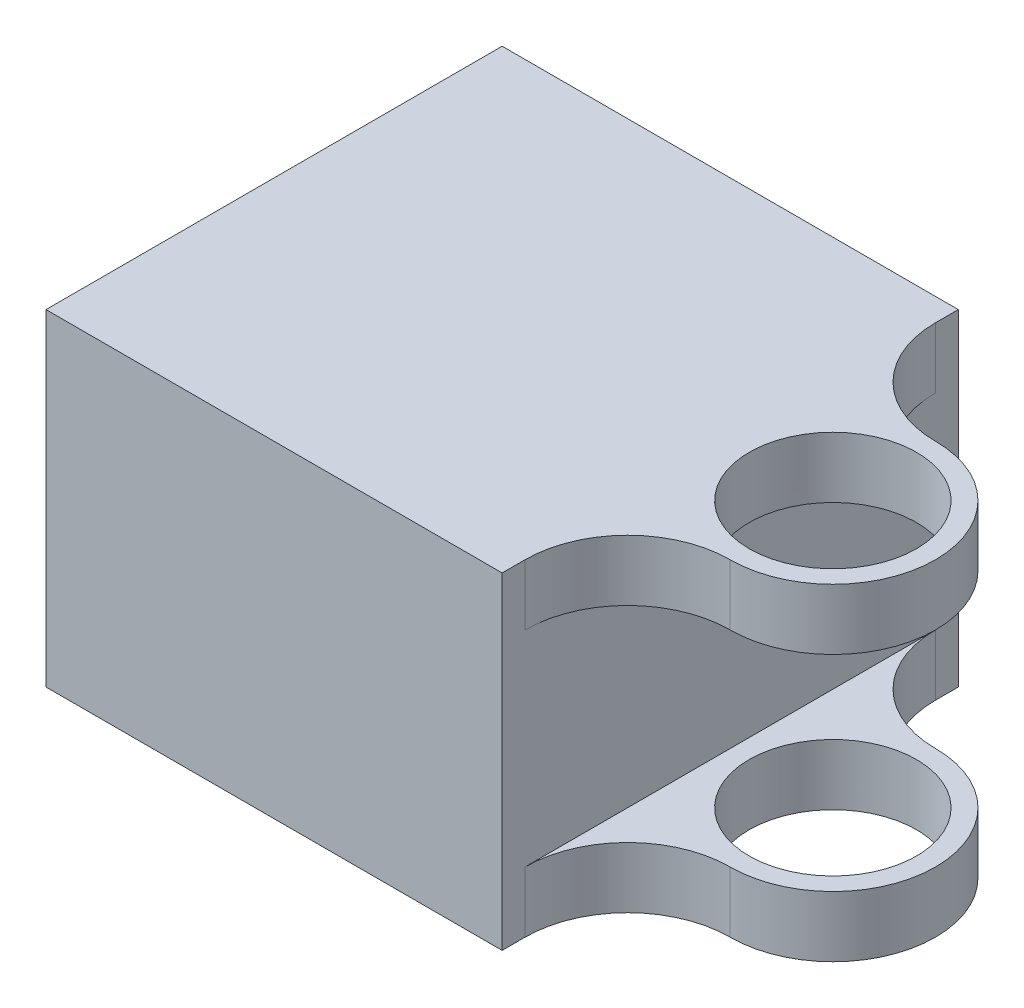
SolidWorks part; units mm, degrees
ref_plane "Спереди" through (0, 0, 0) normal (0, 0, 1) x (1, 0, 0)
ref_plane "Сверху" through (0, 0, 0) normal (0, 1, 0) x (1, 0, 0)
ref_plane "Справа" through (0, 0, 0) normal (1, 0, 0) x (0, 0, -1)
sketch "Эскиз1" plane through (0, 0, 0) normal (0, 1, 0) x (1, 0, 0)
  line L0 (11, 0) -> (13.5, 0)
  line L1 (-13.5, -30) -> (-13.5, 30)
  line L2 (-13.5, 30) -> (-73.5, 30)
  line L3 (-73.5, 30) -> (-73.5, -30)
  line L4 (-73.5, -30) -> (-13.5, -30)
  line L5 (0, -13.5) -> (-13.5, -13.5) construction
  circle A0 centre (0, 0) radius 11
  circle A1 centre (0, 0) radius 13.5
  arc A3 (0, -13.5) -> (-13.5, -27) centre (0, -27) ccw
  arc A5 (-13.5, 27) -> (0, 13.5) centre (0, 27) ccw
  point P9 (-13.5, 0)
extrude "Бобышка-Вытянуть1" add sketch "Эскиз1" along normal mid plane 43 contours A1 A0 | A3 L5 L1 | L5 A1 L1 | A5 L1 A1 | L3 L4 L1 L2 region at (9.2759, 0, 9.2759) region at (-10.4845, 0, -13.5) region at (-10.4845, 0, 16.5155) region at (-10.4845, 0, 10.4845) region at (-43.5, 0, 0)
sketch "Эскиз2" plane through (0, 0, 0) normal (0, 0, 1) x (1, 0, 0)
  line L1 (0, 21.5) -> (0, -21.5) construction
  line L2 (0, 13.5) -> (13.5, 13.5)
  line L3 (13.5, -21.5) -> (13.5, 21.5) construction
  line L4 (13.5, 13.5) -> (13.5, -13.5)
  line L5 (13.5, -13.5) -> (-13.5, -13.5)
  line L6 (-13.5, 21.5) -> (-13.5, -21.5) construction
  line L7 (-13.5, -13.5) -> (-13.5, 13.5)
  line L8 (-13.5, 21.5) -> (-13.5, -21.5) construction
  line L9 (-13.5, 13.5) -> (0, 13.5)
  circle A1 centre (0, 0) radius 13.5
extrude "Вырез-Вытянуть1" cut sketch "Эскиз2" against normal through all both and the other way through all contours A1 | A1 L4 L2 | A1 L9 L7 | A1 L7 L5 | A1 L5 L4 region at (-10.4845, 10.4845, 0) region at (10.4845, 10.4845, 0) region at (0, 0, 0) region at (10.4845, -10.4845, 0) region at (-10.4845, -10.4845, 0)
